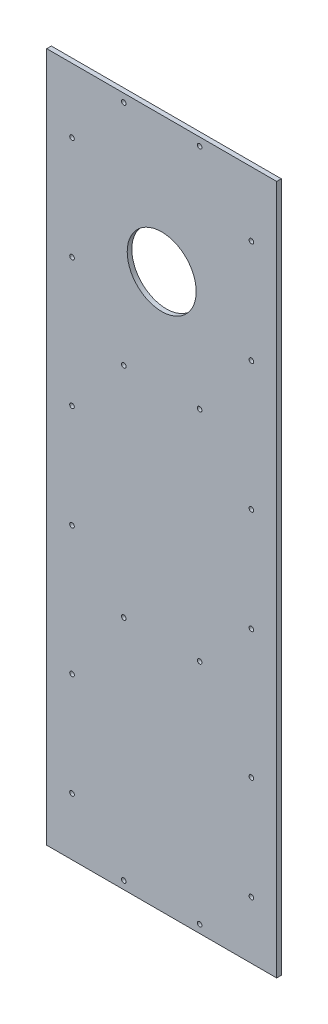
SolidWorks part; units mm, degrees
material "Alumina"
ref_plane "Front Plane" through (0, 0, 0) normal (0, 0, 1) x (1, 0, 0)
ref_plane "Top Plane" through (0, 0, 0) normal (0, 1, 0) x (1, 0, 0)
ref_plane "Right Plane" through (0, 0, 0) normal (1, 0, 0) x (0, 0, -1)
sketch "Sketch1" plane through (0, 0, 0) normal (0, 0, 1) x (1, 0, 0)
  line L1 (50, -150) -> (-50, -150)
  line L2 (50, -150) -> (50, 150)
  line L3 (50, 150) -> (-50, 150)
  line L4 (-50, -150) -> (-50, 150)
  line L5 (50, -150) -> (-50, 150) construction
  line L6 (50, 150) -> (-50, -150) construction
  point P0 (0, 0)
  dimension "D1" = 100
  dimension "D2" = 300
extrude "Boss-Extrude1" add sketch "Sketch1" along normal blind 2
sketch "Sketch2" plane through (0, 0, 2) normal (0, 0, 1) x (1, 0, 0)
  line L0 (-50, 150) -> (-50, -150) construction
  line L1 (50, 150) -> (-50, 150) construction
  line L2 (-50, -150) -> (50, -150) construction
  line L4 (0, -1.1) -> (0, 1.1) construction
  line L5 (-39, 122) -> (-39, 21) construction
  circle A0 centre (-39, 122) radius 1
  circle A1 centre (-39, 77) radius 1
  circle A2 centre (39, 122) radius 1
  circle A3 centre (39, 77) radius 1
  circle A4 centre (-39, 21) radius 1
  circle A5 centre (-39, -24) radius 1
  circle A6 centre (39, 21) radius 1
  circle A7 centre (39, -24) radius 1
  circle A8 centre (-39, -80) radius 1
  circle A9 centre (-39, -125) radius 1
  circle A10 centre (39, -80) radius 1
  circle A11 centre (39, -125) radius 1
  circle A13 centre (16.5, -146.5) radius 1
  circle A14 centre (-16.5, -146.5) radius 1
  circle A15 centre (-16.5, 146.5) radius 1
  circle A16 centre (16.5, 146.5) radius 1
  dimension "D1" = 2
  dimension "D3" = 28
  dimension "D4" = 2
  dimension "D6" = 11
  dimension "D10" = 2
  dimension "D11" = 33
  dimension "D13" = 3.5
  dimension "D14" = 78
  dimension "D15" = 11
  dimension "D5" = 3.5
  dimension "D2" = 11
  dimension "D9" = 25
  dimension "D17" = 101
  dimension "D7" = 2
  dimension "D8" = 3
  dimension "D12" = 2
extrude "Cut-Extrude1" cut sketch "Sketch2" against normal blind 10
sketch "Sketch3" plane through (0, 0, 0) normal (0, 0, -1) x (-1, 0, 0)
  line L0 (-50, 150) -> (50, 150) construction
  line L1 (-50, -150) -> (-50, 150) construction
  circle A0 centre (0, 91) radius 15
  dimension "D2" = 30
  dimension "D3" = 50
  dimension "D1" = 59
extrude "Cut-Extrude2" cut sketch "Sketch3" against normal blind 10
sketch "Sketch5" plane through (0, 0, 2) normal (0, 0, 1) x (1, 0, 0)
  line L0 (-16.5, 47.5) -> (-16.5, -47.5) construction
  line L1 (-16.5, -47.5) -> (16.5, -47.5) construction
  line L2 (16.5, -47.5) -> (16.5, 47.5) construction
  line L3 (16.5, 47.5) -> (-16.5, 47.5) construction
  line L4 (-16.5, 146.5) -> (-16.5, 47.5) construction
  line L5 (16.5, 146.5) -> (16.5, 47.5) construction
  circle A6 centre (-16.5, 47.5) radius 1
  circle A7 centre (16.5, 47.5) radius 1
  circle A8 centre (-16.5, -47.5) radius 1
  circle A9 centre (16.5, -47.5) radius 1
  circle A10 centre (-16.5, 146.5) radius 1 construction
  circle A11 centre (16.5, 146.5) radius 1 construction
  dimension "D1" = 99
  dimension "D3" = 2
  dimension "D4" = 2
  dimension "D5" = 2
  dimension "D6" = 2
  dimension "D2" = 95
extrude "Cut-Extrude3" cut sketch "Sketch5" against normal blind 10
